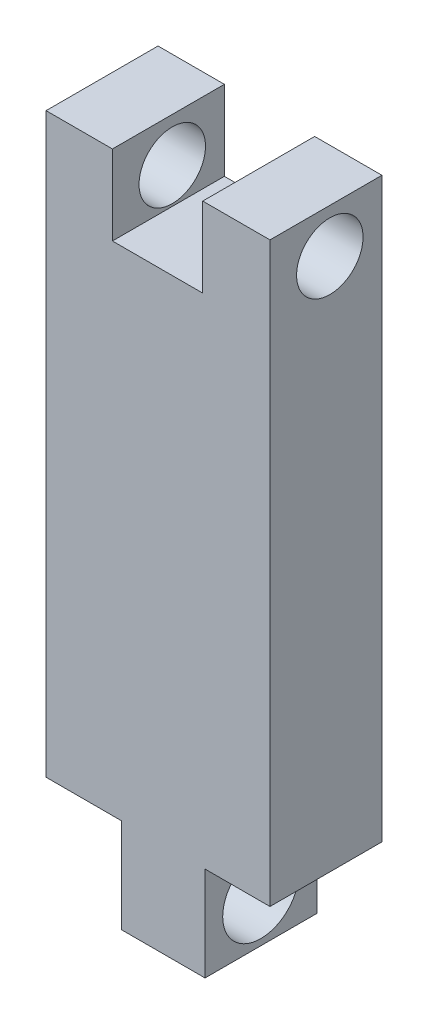
SolidWorks part; units mm, degrees
ref_plane "Front Plane" through (0, 0, 0) normal (0, 0, 1) x (1, 0, 0)
ref_plane "Top Plane" through (0, 0, 0) normal (0, 1, 0) x (1, 0, 0)
ref_plane "Right Plane" through (0, 0, 0) normal (1, 0, 0) x (0, 0, -1)
sketch "Sketch1" plane through (0, 0, 0) normal (0, 0, 1) x (1, 0, 0)
  line L1 (0, 0) -> (25.4, 0)
  line L2 (0, 0) -> (0, 76.2)
  line L3 (0, 76.2) -> (25.4, 76.2)
  line L4 (25.4, 0) -> (25.4, 76.2)
  dimension "D1" = 25.4
  dimension "D2" = 76.2
extrude "Boss-Extrude1" add sketch "Sketch1" along normal blind 12.7
sketch "Sketch5" plane through (0, 0, 12.7) normal (0, 0, 1) x (1, 0, 0)
  line L0 (7.5277, 76.2) -> (7.5277, 67.1563)
  line L1 (25.4, 76.2) -> (0, 76.2) construction
  line L2 (7.5277, 67.1563) -> (17.7709, 67.1563)
  line L3 (17.7709, 67.1563) -> (17.7709, 76.2)
  line L4 (17.7709, 76.2) -> (7.5277, 76.2)
extrude "Cut-Extrude1" cut sketch "Sketch5" against normal through all
sketch "Sketch6" plane through (0, 0, 0) normal (-1, 0, 0) x (0, 0, 1)
  circle A0 centre (5.9099, 71.2041) radius 3.7719
extrude "Cut-Extrude2" cut sketch "Sketch6" against normal through all
sketch "Sketch7" plane through (0, 0, 12.7) normal (0, 0, 1) x (1, 0, 0)
  line L0 (0, 10.7048) -> (8.543, 10.7048)
  line L1 (0, 76.2) -> (0, 0) construction
  line L2 (8.543, 10.7048) -> (8.543, 0)
  line L3 (0, 0) -> (25.4, 0) construction
  line L4 (8.543, 0) -> (0, 0)
  line L5 (0, 0) -> (0, 10.7048)
  line L6 (25.4, 10.7048) -> (18.0344, 10.7048)
  line L7 (25.4, 0) -> (25.4, 76.2) construction
  line L8 (18.0344, 10.7048) -> (18.0344, 0)
  line L9 (18.0344, 0) -> (25.4, 0)
  line L10 (25.4, 0) -> (25.4, 10.7048)
extrude "Cut-Extrude3" cut sketch "Sketch7" against normal through all
sketch "Sketch8" plane through (8.543, 0, 0) normal (-1, 0, 0) x (0, 0, 1)
  circle A0 centre (6.3802, 5.0254) radius 4.3186
extrude "Cut-Extrude4" cut sketch "Sketch8" against normal through all
